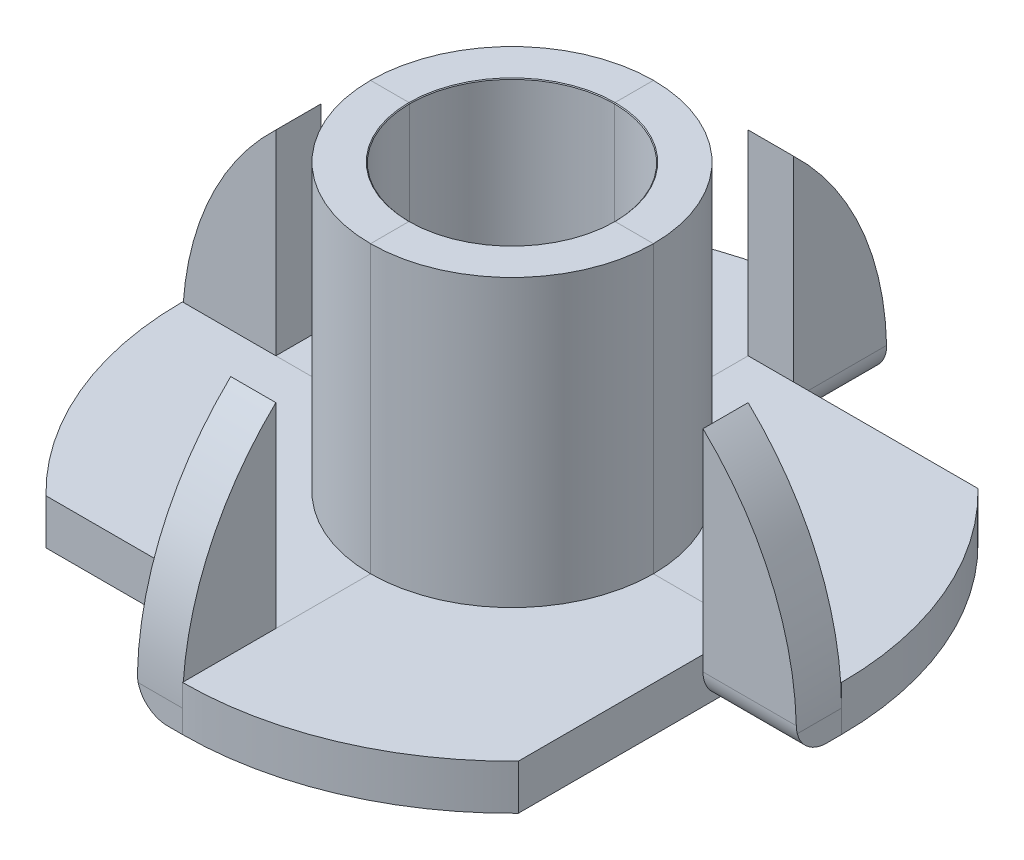
SolidWorks part; units mm, degrees
material "Alloy Steel"
ref_plane "Front Plane" through (0, 0, 0) normal (0, 0, 1) x (1, 0, 0)
ref_plane "Top Plane" through (0, 0, 0) normal (0, 1, 0) x (1, 0, 0)
ref_plane "Right Plane" through (0, 0, 0) normal (1, 0, 0) x (0, 0, -1)
sketch "Sketch1" plane through (0, 0, 0) normal (0, 1, 0) x (1, 0, 0)
  line L4 (0, 0) -> (0, 10.95) construction
  line L5 (0, 0) -> (-10.95, 0) construction
  line L6 (-10.95, 0) -> (0, 0)
  line L7 (0, 0) -> (0, 10.95)
  arc A0 (0, 10.95) -> (-10.95, 0) centre (0, 0) ccw
  dimension "D1" = 21.9
extrude "Boss-Extrude1" add sketch "Sketch1" along normal blind 1.5
sketch "Sketch2" plane through (0, 0, 0) normal (0, 1, 0) x (1, 0, 0)
  line L0 (-10.95, 0) -> (0, 0) construction
  line L1 (-10.8468, 9.5) -> (-7.8468, 9.5)
  line L2 (-10.8468, 9.5) -> (-10.8468, 1.5)
  line L3 (-10.8468, 1.5) -> (-7.8468, 1.5)
  line L4 (-7.8468, 9.5) -> (-7.8468, 1.5)
  arc A0 (0, 10.95) -> (-10.95, 0) centre (0, 0) ccw construction
  point P4 (0, 0)
  dimension "D1" = 1.5
  dimension "D2" = 3
  dimension "D3" = 8
extrude "Cut-Extrude1" cut sketch "Sketch2" along normal blind 1.5
sketch "Sketch3" plane through (0, 0, 0) normal (0, 1, 0) x (1, 0, 0)
  line L1 (-7.8468, 1.5) -> (-10.95, 1.5)
  line L2 (-7.8468, 1.5) -> (-7.8468, 0)
  line L3 (-7.8468, 0) -> (-10.95, 0)
  line L4 (-10.95, 1.5) -> (-10.95, 0)
extrude "Boss-Extrude2" add sketch "Sketch3" along normal blind 8
fillet "Fillet1" radius 10 1 edges at (-10.95, 8, -0.75)
fillet "Fillet2" radius 1 1 edges at (-9.3984, 0, -1.5)
sketch "Sketch4" plane through (0, 0, 0) normal (0, 1, 0) x (1, 0, 0)
  line L0 (0, 0) -> (0, 4.7)
  line L1 (0, 0) -> (-4.7, 0)
  arc A0 (0, 4.7) -> (-4.7, 0) centre (0, 0) ccw
  dimension "D1" = 9.4
extrude "Boss-Extrude3" add sketch "Sketch4" along normal blind 11
pattern_circular "CirPattern1" count 4 over 360 about axis through (0, 1.5, 0) along (0, -1, 0) of bodies 104
hole_wizard "Tap Drill for M8 Tap1" positions "Sketch5" profile "Sketch6" hole size "M8" standard "ISO" end condition through all
sketch "Sketch5" plane through (0, 11, 0) normal (0, 1, 0) x (1, 0, 0)
  point P0 (0, 0)
sketch "Sketch6" plane through (0, 11, 0) normal (1, 0, 0) x (0, 0, 1)
  line L0 (0, 0) -> (0, 11)
  line L1 (0, 11) -> (3.4, 11)
  line L2 (3.4, 11) -> (3.4, 0.025)
  line L3 (3.4, 0.025) -> (3.425, 0)
  line L5 (3.425, 0) -> (0, 0)
  line L6 (-3.4, 0.025) -> (-3.425, 0) construction
  line L11 (0, -6.35) -> (0, 107.95) construction
  dimension "Thru Hole Dia." = 6.8
  dimension "Thru Hole Depth" = 11
  dimension "Near C'Sink Dia." = 6.85
  dimension "Near C'Sink Angle" = 90
cosmetic thread "Cosmetic Thread1" parameters "D2"=8
cosmetic thread "Cosmetic Thread2" parameters "D2"=8
cosmetic thread "Cosmetic Thread3" parameters "D2"=8
cosmetic thread "Cosmetic Thread4" parameters "D2"=8
